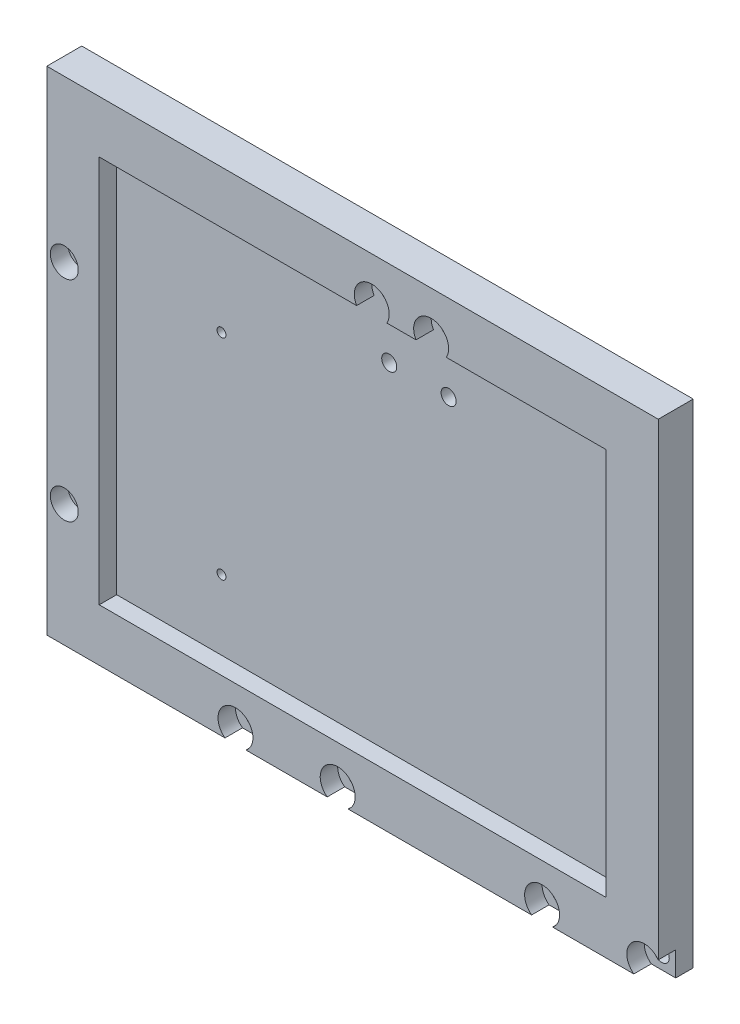
SolidWorks part; units mm, degrees
material "ABS"
ref_plane "Front Plane" through (0, 0, 0) normal (0, 0, 1) x (1, 0, 0)
ref_plane "Top Plane" through (0, 0, 0) normal (0, 1, 0) x (1, 0, 0)
ref_plane "Right Plane" through (0, 0, 0) normal (1, 0, 0) x (0, 0, -1)
sketch "Sketch1" plane through (0, 0, 0) normal (0, 0, 1) x (1, 0, 0)
  line L0 (58.5, -66.5) -> (-58.5, -66.5) construction
  line L1 (-62.5, -70.5) -> (62.5, -70.5)
  line L2 (-62.5, -70.5) -> (-62.5, 70.5)
  line L3 (-62.5, 70.5) -> (62.5, 70.5)
  line L4 (62.5, -70.5) -> (62.5, 70.5)
  line L5 (-62.5, -70.5) -> (62.5, 70.5) construction
  line L6 (-62.5, 70.5) -> (62.5, -70.5) construction
  line L7 (-19.5, 41) -> (-2.5, 41) construction
  line L8 (-19.5, 41) -> (-19.5, 58) construction
  line L9 (-19.5, 58) -> (-2.5, 58) construction
  line L10 (-2.5, 41) -> (-2.5, 58) construction
  line L11 (-19.5, 41) -> (-2.5, 58) construction
  line L12 (-19.5, 58) -> (-2.5, 41) construction
  line L13 (62.5, -62.5) -> (-62.5, -62.5) construction
  line L14 (62.5, -62.5) -> (62.5, -70.5) construction
  line L15 (62.5, -70.5) -> (-62.5, -70.5) construction
  line L16 (-62.5, -62.5) -> (-62.5, -70.5) construction
  line L17 (62.5, -62.5) -> (-62.5, -70.5) construction
  line L18 (62.5, -70.5) -> (-62.5, -62.5) construction
  line L19 (29.25, -66.5) -> (-29.25, -66.5) construction
  line L20 (-58.5, -66.5) -> (-29.25, -66.5) construction
  line L21 (-29.25, -66.5) -> (0, -66.5) construction
  circle A0 centre (-19.5, 58) radius 2.15
  circle A1 centre (-2.5, 58) radius 2.15
  circle A2 centre (-2.5, 41) radius 2.15
  circle A3 centre (-19.5, 41) radius 2.15
  circle A4 centre (-58.5, -66.5) radius 4 construction
  circle A5 centre (-58.5, -66.5) radius 2.15
  circle A6 centre (58.5, -66.5) radius 2.15
  circle A7 centre (-29.25, -66.5) radius 2.15
  circle A8 centre (29.25, -66.5) radius 2.15
  point P0 (0, 0)
  point P6 (-11, 49.5)
  point P15 (0, -66.5)
  point P21 (0, -66.5)
  point P27 (0, -66.5)
  dimension "D3" = 4.3
  dimension "D2" = 12.5
  dimension "D1" = 125
  dimension "D4" = 17
  dimension "D5" = 65
  dimension "D6" = 120
  dimension "D7" = 8
extrude "Boss-Extrude1" add sketch "Sketch1" along normal mid plane 5
sketch "Sketch2" plane through (0, 0, -2.5) normal (0, 0, -1) x (-1, 0, 0)
  line L0 (62.5, 70.5) -> (62.5, -70.5) construction
  line L1 (62.5, 29.5) -> (112.5, 29.5) construction
  line L2 (62.5, 29.5) -> (62.5, -40.5) construction
  line L3 (62.5, -40.5) -> (112.5, -40.5) construction
  line L4 (112.5, 29.5) -> (112.5, -40.5) construction
  line L5 (62.5, -70.5) -> (-62.5, -70.5) construction
  line L6 (62.5, 29.5) -> (112.5, -40.5) construction
  line L7 (62.5, -40.5) -> (112.5, 29.5) construction
  line L8 (-62.5, 70.5) -> (62.5, 70.5) construction
  line L9 (107.5, -35.5) -> (67.5, -35.5) construction
  line L10 (107.5, -35.5) -> (107.5, 24.5) construction
  line L11 (107.5, 24.5) -> (67.5, 24.5) construction
  line L12 (67.5, -35.5) -> (67.5, 24.5) construction
  line L13 (107.5, -35.5) -> (67.5, 24.5) construction
  line L14 (107.5, 24.5) -> (67.5, -35.5) construction
  line L15 (62.5, -70.5) -> (112.5, -70.5)
  line L16 (62.5, -70.5) -> (62.5, 70.5)
  line L17 (62.5, 70.5) -> (112.5, 70.5)
  line L18 (112.5, -70.5) -> (112.5, 70.5)
  circle A0 centre (67.5, 24.5) radius 1.275
  circle A1 centre (107.5, 24.5) radius 1.275
  circle A2 centre (67.5, -35.5) radius 1.275
  circle A3 centre (107.5, -35.5) radius 1.275
  point P8 (87.5, -5.5)
  point P9 (87.5, -5.5)
  dimension "D6" = 2.55
  dimension "D1" = 30
  dimension "D2" = 50
  dimension "D3" = 70
  dimension "D4" = 40
  dimension "D5" = 60
extrude "Boss-Extrude2" add sketch "Sketch2" against normal up to surface (5 mm away) up to face at (0, 0, 2.5)
sketch "Sketch3" plane through (0, 0, 2.5) normal (0, 0, 1) x (1, 0, 0)
  line L5 (-112.5, 70.5) -> (62.5, 70.5)
  line L6 (-112.5, 70.5) -> (-112.5, -70.5)
  line L7 (-112.5, -70.5) -> (62.5, -70.5)
  line L8 (47.5, -55.5) -> (47.5, 55.5)
  line L9 (47.5, 55.5) -> (-97.5, 55.5)
  line L10 (-97.5, 55.5) -> (-97.5, -55.5)
  line L11 (-97.5, -55.5) -> (47.5, -55.5)
  line L12 (47.5, -55.5) -> (47.5, 55.5)
  line L13 (47.5, 55.5) -> (-97.5, 55.5)
  line L14 (-97.5, 55.5) -> (-97.5, -55.5)
  line L15 (-97.5, -55.5) -> (47.5, -55.5)
  line L16 (62.5, 70.5) -> (62.5, -70.5)
  circle A2 centre (-107.5, 24.5) radius 4
  circle A3 centre (-107.5, -35.5) radius 4
  circle A4 centre (-58.5, -66.5) radius 5
  circle A5 centre (-29.25, -66.5) radius 5
  circle A6 centre (29.25, -66.5) radius 5
  circle A7 centre (58.5, -66.5) radius 5
  circle A8 centre (-19.5, 58) radius 5
  circle A9 centre (-2.5, 58) radius 5
  line M6 (62.5, -70.5) -> (62.5, 70.5)
  line M7 (62.5, 70.5) -> (-112.5, 70.5)
  line M8 (-112.5, 70.5) -> (-112.5, -70.5)
  line M9 (-112.5, -70.5) -> (62.5, -70.5)
  dimension "D2" = 8
  dimension "D3" = 10
  dimension "D1" = 15
extrude "Boss-Extrude3" add sketch "Sketch3" along normal blind 5 contours A7 A4 A5 A6 A9 L13 L12 L15 L14 A8 A3 A2 M6 M7 M8 M9 region at (-25, 68.2526, 2.5)
